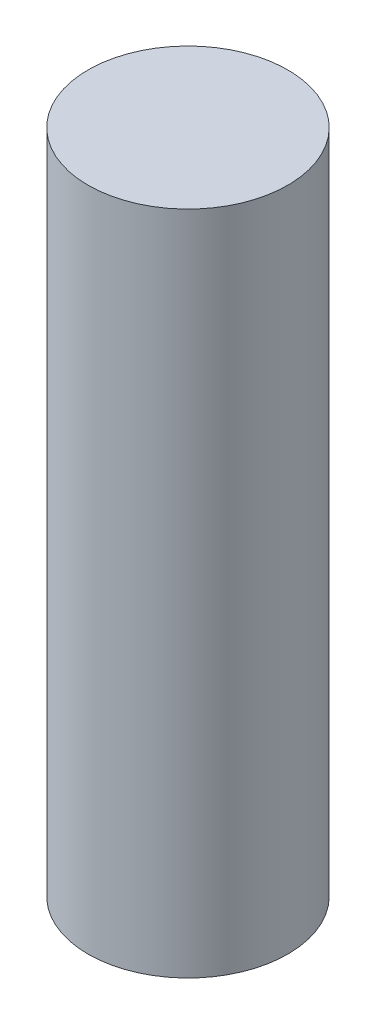
SolidWorks part; units mm, degrees
ref_plane "Front Plane" through (0, 0, 0) normal (0, 0, 1) x (1, 0, 0)
ref_plane "Top Plane" through (0, 0, 0) normal (0, 1, 0) x (1, 0, 0)
ref_plane "Right Plane" through (0, 0, 0) normal (1, 0, 0) x (0, 0, -1)
ref_axis "Axis1" through (0, 55, 0) along (0, -1, 0)
ref_plane "Plane1" through (0, 0, 0) normal (0, 1, 0) x (1, 0, 0)
sketch "Sketch1" plane through (0, 0, 0) normal (0, 1, 0) x (1, 0, 0)
  circle A0 centre (0, 0) radius 1.5
  dimension "D1" = 3
extrude "Boss-Extrude1" add sketch "Sketch1" against normal blind 10
